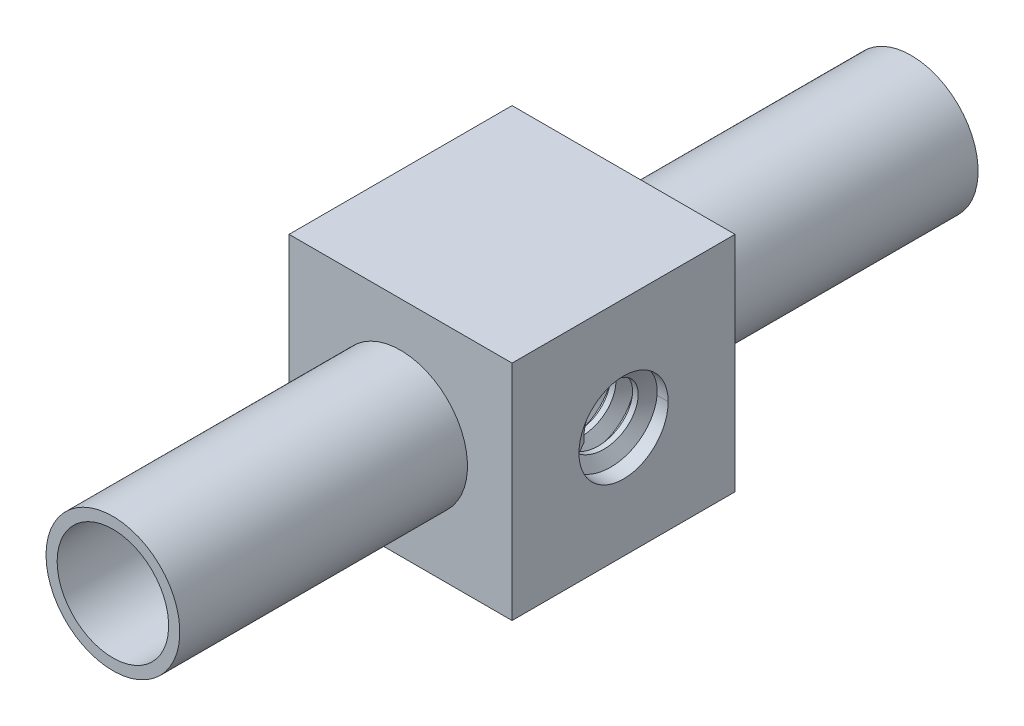
SolidWorks part; units mm, degrees
ref_plane "Front Plane" through (0, 0, 0) normal (0, 0, 1) x (1, 0, 0)
ref_plane "Top Plane" through (0, 0, 0) normal (0, 1, 0) x (1, 0, 0)
ref_plane "Right Plane" through (0, 0, 0) normal (1, 0, 0) x (0, 0, -1)
sketch "Sketch2" plane through (0, 0, 0) normal (0, 0, 1) x (1, 0, 0)
  circle A0 centre (0, 0) radius 5
  circle A1 centre (0, 0) radius 6
  dimension "D1" = 10
  dimension "D2" = 1
extrude "Boss-Extrude1" add sketch "Sketch2" along normal blind 71.6
sketch "Sketch3" plane through (0, 0, 0) normal (1, 0, 0) x (0, 0, -1)
  line L0 (0, 0) -> (-71.6, 0) construction
  line L1 (-71.6, 6) -> (-71.6, -6) construction
  line L2 (-35.8, 0) -> (-35.8, 24.4946) construction
  line L4 (-45.8, -10) -> (-25.8, -10)
  line L5 (-45.8, -10) -> (-45.8, 10)
  line L6 (-45.8, 10) -> (-25.8, 10)
  line L7 (-25.8, -10) -> (-25.8, 10)
  line L8 (-45.8, -10) -> (-25.8, 10) construction
  line L9 (-45.8, 10) -> (-25.8, -10) construction
  dimension "D1" = 20
  dimension "D2" = 20
extrude "Boss-Extrude2" add sketch "Sketch3" along normal mid plane 20
sketch "Sketch4" plane through (10, 0, 0) normal (1, 0, 0) x (0, 0, -1)
  line L0 (-35.8, 10) -> (-35.8, -10) construction
  line L1 (-25.8, 10) -> (-45.8, 10) construction
  line L2 (-45.8, -10) -> (-25.8, -10) construction
  circle A0 centre (-35.8, 0) radius 4
  dimension "D1" = 8
extrude "Cut-Extrude1" cut sketch "Sketch4" against normal through all
thread "Thread1" pitch 2 method extrude profile "Thread Profile1" start angle 0, offset 0, length 18, pitch 2, diameter 8
ref_plane "Plane1" through (10, 0, 39.8) normal (0, -1, 0) x (0, 0, 1)
sketch "Thread Profile1" plane through (10, 0, 39.8) normal (0, -1, 0) x (0, 0, 1)
  line L0 (0, 0) -> (0, 2) construction
  line L11 (0, 0) -> (0, 1.75)
  line L12 (0, 1.75) -> (-1.0825, 1.125)
  line L13 (-1.0825, 1.125) -> (-1.0825, 0.625)
  line L15 (-1.0825, 0.625) -> (0, 0)
  line L17 (-1.0825, 0.875) -> (0, 0.875) construction
  point P2 (0, 0)
  dimension "Pitch" = 2
  dimension "Profile_Angle" = 60
  dimension "Profile_Land" = 0.5
  dimension "Profile_Height" = 1.0825
